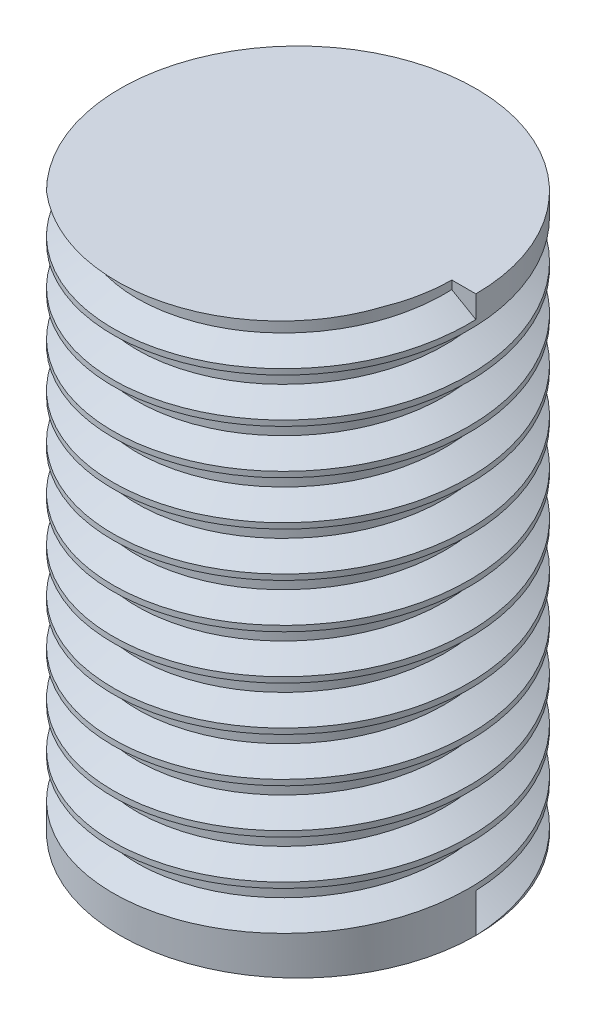
SolidWorks part; units mm, degrees
ref_plane "前视基准面" through (0, 0, 0) normal (0, 0, 1) x (1, 0, 0)
ref_plane "上视基准面" through (0, 0, 0) normal (0, 1, 0) x (1, 0, 0)
ref_plane "右视基准面" through (0, 0, 0) normal (1, 0, 0) x (0, 0, -1)
other "Configuration Table"
sketch "草图1" plane through (0, 0, 0) normal (0, 0, 1) x (1, 0, 0)
  line L0 (0, 0) -> (8, 0)
  line L1 (8, 0) -> (8, 25)
  line L2 (8, 25) -> (0, 25)
  line L3 (0, 25) -> (0, 0)
  line L4 (0, 0) -> (0, 25) construction
  dimension "radius" = 8
  dimension "height" = 25
revolve "Revolve" add sketch "草图1" angle 360 about L4
thread "Thread" pitch 2 method cut profile "螺纹线轮廓1" start angle 0, offset 0, length 24, pitch 2, diameter 16
ref_plane "基准面1" through (8, 0, 0) normal (0, 0, 1) x (1, 0, 0)
sketch "螺纹线轮廓1" plane through (8, 0, 0) normal (0, 0, 1) x (1, 0, 0)
  line L0 (0, 0) -> (0, 2) construction
  line L11 (0, 0) -> (0, 1.75)
  line L12 (0, 1.75) -> (-1.0825, 1.125)
  line L13 (-1.0825, 1.125) -> (-1.0825, 0.625)
  line L15 (-1.0825, 0.625) -> (0, 0)
  line L17 (-1.0825, 0.875) -> (0, 0.875) construction
  point P2 (0, 0)
  dimension "Pitch" = 2
  dimension "Profile_Angle" = 60
  dimension "Profile_Land" = 0.5
  dimension "Profile_Height" = 1.0825
